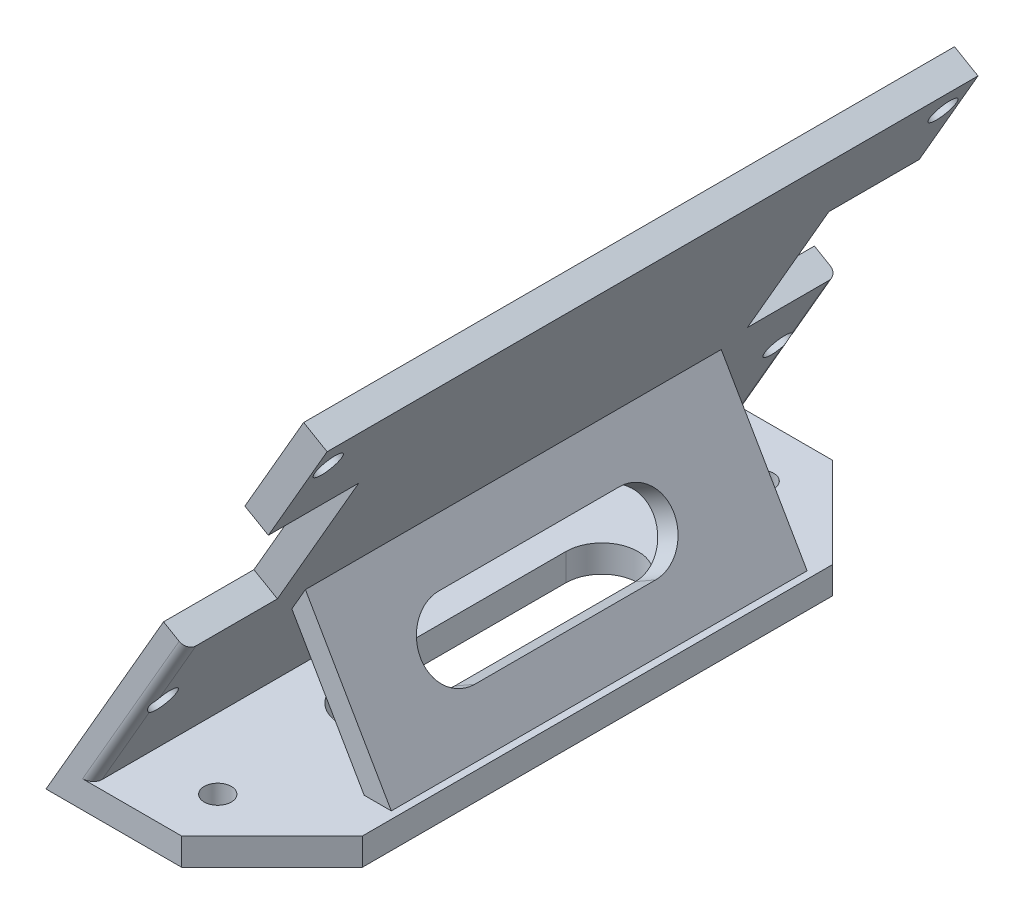
SolidWorks part; units mm, degrees
material "聚脂树脂"
ref_plane "前视基准面" through (0, 0, 0) normal (0, 0, 1) x (1, 0, 0)
ref_plane "上视基准面" through (0, 0, 0) normal (0, 1, 0) x (1, 0, 0)
ref_plane "右视基准面" through (0, 0, 0) normal (1, 0, 0) x (0, 0, -1)
other "Configuration Table"
sketch "草图2" plane through (0, 0, 0) normal (0, 0, 1) x (1, 0, 0)
  line L0 (0, 0) -> (0, 88.747) construction
  line L1 (0, 0) -> (110.2523, 0) construction
  line L2 (0, 0) -> (28.5, 49.3634)
  line L3 (28.5, 49.3634) -> (31.0981, 47.8634)
  line L4 (31.0981, 47.8634) -> (5.1962, 3)
  line L5 (5.1962, 3) -> (25, 3)
  line L6 (25, 3) -> (25, 0)
  line L7 (25, 0) -> (0, 0)
  dimension "D1" = 60
  dimension "D2" = 3
  dimension "D3" = 3
  dimension "D4" = 25
  dimension "D5" = 57
extrude "凸台-拉伸1" add sketch "草图2" along normal blind 36 and the other way blind 36
sketch "草图3" plane through (0, 0, 36) normal (0, 0, 1) x (1, 0, 0)
  line L0 (0, 0) -> (0, 52.6153) construction
  line L1 (0, 0) -> (59.4187, 0) construction
  line L2 (13.1962, 16.8564) -> (14.6962, 19.4545)
  line L3 (5.1962, 3) -> (31.0981, 47.8634) construction
  line L4 (14.6962, 19.4545) -> (24.1962, 3)
  line L5 (25, 3) -> (5.1962, 3) construction
  line L6 (24.1962, 3) -> (21.1962, 3)
  line L7 (21.1962, 3) -> (13.1962, 16.8564)
  dimension "D1" = 3
  dimension "D2" = 3
  dimension "D3" = 16
extrude "凸台-拉伸2" add sketch "草图3" against normal blind 60
sketch "草图4" plane through (0, 0, 0) normal (-0.866, 0.5, 0) x (0, 0, 1)
  line L0 (0, 0) -> (0, 67.8979) construction
  line L1 (0, 0) -> (54.9113, 0) construction
  line L2 (0, 35) -> (62.8022, 35) construction
  line L3 (36, 26) -> (36, 44)
  line L4 (36, 57) -> (36, 0) construction
  line L5 (36, 44) -> (26, 44)
  line L6 (26, 44) -> (26, 26)
  line L7 (36, 26) -> (26, 26)
  line L8 (-36, 26) -> (-26, 26)
  line L9 (-26, 44) -> (-26, 26)
  line L10 (-36, 44) -> (-26, 44)
  line L11 (-36, 26) -> (-36, 44)
  circle A0 centre (34, 53.25) radius 1.5
  circle A1 centre (34, 16.75) radius 1.5
  circle A2 centre (-34, 16.75) radius 1.5
  circle A3 centre (-34, 53.25) radius 1.5
  point P21 (36, 35)
  point P22 (26, 35)
  dimension "D1" = 3
  dimension "D2" = 68
  dimension "D3" = 36.5
  dimension "D4" = 35
  dimension "D5" = 9
  dimension "D6" = 10
extrude "切除-拉伸1" cut sketch "草图4" against normal blind 6
sketch "草图6" plane through (0, 0, 36) normal (0, 0, 1) x (1, 0, 0)
  line L7 (24.1962, 3) -> (14.6962, 19.4545) construction
  line L8 (13.1962, 16.8564) -> (21.1962, 3) construction
  line L9 (24.1962, 3) -> (14.6962, 19.4545)
  line L10 (13.1962, 16.8564) -> (21.1962, 3)
  line L11 (14.6962, 19.4545) -> (13.1962, 16.8564)
  line L12 (21.1962, 3) -> (24.1962, 3)
extrude "切除-拉伸3" cut sketch "草图6" against normal blind 14
sketch "草图9" plane through (0, 0, 0) normal (0, -1, 0) x (1, 0, 0)
  line L0 (0, 0) -> (73.7033, 0) construction
  line L1 (13, -12.5) -> (13, 12.5) construction
  line L4 (9, -12.5) -> (9, 12.5)
  line L5 (17, -12.5) -> (17, 12.5)
  line L6 (0, -36) -> (0, 36) construction
  arc A2 (9, -12.5) -> (17, -12.5) centre (13, -12.5) ccw
  arc A3 (17, 12.5) -> (9, 12.5) centre (13, 12.5) ccw
  circle A4 centre (13, 30) radius 1.5
  circle A5 centre (13, -30) radius 1.5
  point P5 (13, 0)
  dimension "D2" = 4
  dimension "D4" = 3
  dimension "D6" = 60
  dimension "D1" = 25
  dimension "D3" = 13
  dimension "D5" = 13
extrude "切除-拉伸5" cut sketch "草图9" against normal blind 6
sketch "草图11" plane through (19.4462, 11.2272, 0) normal (0.866, 0.5, 0) x (0, 0, -1)
  line L0 (-10, 0) -> (10, 0) construction
  line L1 (-10, 4) -> (10, 4)
  line L2 (-10, -4) -> (10, -4)
  arc A0 (-10, 4) -> (-10, -4) centre (-10, 0) ccw
  arc A1 (10, -4) -> (10, 4) centre (10, 0) ccw
  point P2 (0, 0)
  dimension "D2" = 4
  dimension "D1" = 20
extrude "切除-拉伸6" cut sketch "草图11" against normal blind 3
fillet "圆角1" radius 1 2 edges at (10.3971, 12.0083, 36) (10.3971, 12.0083, -36)
chamfer "倒角1" distance 10 angle 45 2 edges at (25, 1.5, -36) (25, 1.5, 36)
